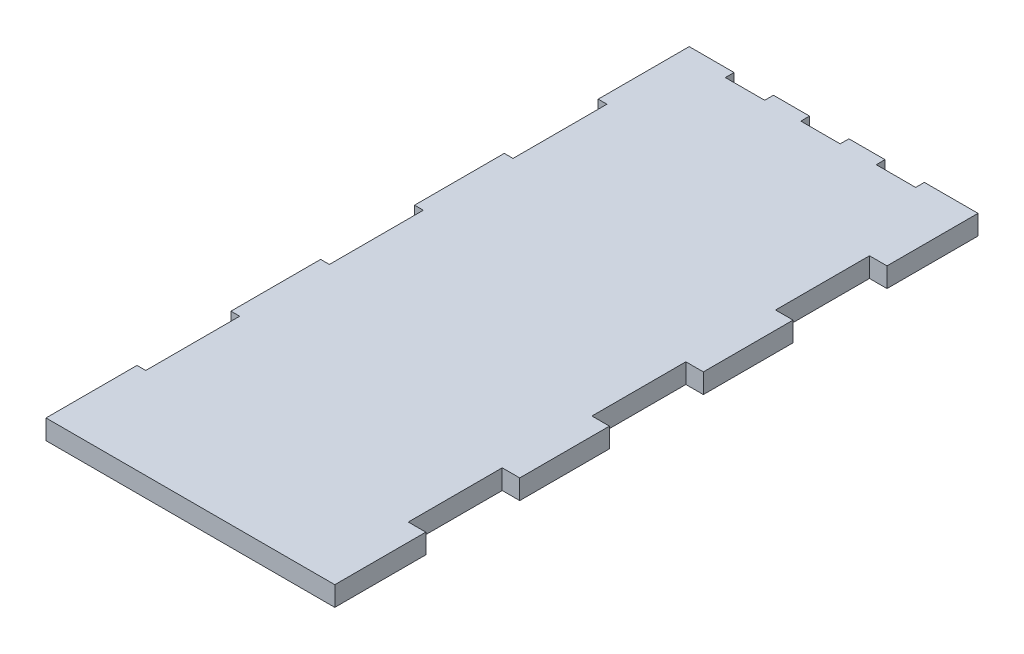
SolidWorks part; units mm, degrees
ref_plane "前视基准面" through (0, 0, 0) normal (0, 0, 1) x (1, 0, 0)
ref_plane "上视基准面" through (0, 0, 0) normal (0, 1, 0) x (1, 0, 0)
ref_plane "右视基准面" through (0, 0, 0) normal (1, 0, 0) x (0, 0, -1)
other "Configuration Table"
sketch "草图4" plane through (0, 0, 0) normal (0, 1, 0) x (1, 0, 0)
  line L6 (-30, -72.5) -> (30, -72.5)
  line L11 (-30, -72.5) -> (-30, 72.5)
  line L12 (-30, 72.5) -> (30, 72.5)
  line L13 (30, -72.5) -> (30, 72.5)
  line L14 (-30, -72.5) -> (30, 72.5) construction
  line L15 (-30, 72.5) -> (30, -72.5) construction
  point P0 (0, 0)
  dimension "D1" = 60
  dimension "D2" = 145
extrude "凸台-拉伸1" add sketch "草图4" along normal blind 4.5
sketch "草图5" plane through (0, 0, -72.5) normal (0, 0, -1) x (-1, 0, 0)
  line L0 (-30, 4.5) -> (30, 4.5) construction
  line L1 (30, 0) -> (21.75, 0)
  line L2 (30, 0) -> (30, 4.5)
  line L3 (30, 4.5) -> (21.75, 4.5)
  line L4 (21.75, 0) -> (21.75, 4.5)
  line L5 (-30, 0) -> (30, 0) construction
  line L6 (12.75, 0) -> (4.5, 0)
  line L7 (12.75, 0) -> (12.75, 4.5)
  line L8 (12.75, 4.5) -> (4.5, 4.5)
  line L9 (4.5, 0) -> (4.5, 4.5)
  line L10 (21.75, 0) -> (12.75, 0)
  line L11 (-4.5, 0) -> (-12.75, 0)
  line L12 (-4.5, 0) -> (-4.5, 4.5)
  line L13 (-4.5, 4.5) -> (-12.75, 4.5)
  line L14 (-12.75, 0) -> (-12.75, 4.5)
  line L15 (-21.75, 0) -> (-30, 0)
  line L16 (-21.75, 0) -> (-21.75, 4.5)
  line L17 (-21.75, 4.5) -> (-30, 4.5)
  line L18 (-30, 0) -> (-30, 4.5)
  line L19 (4.5, 0) -> (-4.5, 0)
  line L20 (-12.75, 0) -> (-21.75, 0)
  line M17 (-30, 0) -> (30, 0)
  line M18 (30, 0) -> (30, 4.5)
  line M19 (30, 4.5) -> (-30, 4.5)
  line M20 (-30, 4.5) -> (-30, 0)
  dimension "D1" = 9
extrude "凸台-拉伸2" add sketch "草图5" along normal blind 2 contours L16 M17 M19 M20 | L14 L12 M17 M19 | L9 L7 M17 M19 | L4 M17 M18 M19 region at (-25.875, 2.25, -72.5) region at (-8.625, 2.25, -72.5) region at (8.625, 2.25, -72.5) region at (25.875, 2.25, -72.5)
sketch "草图7" plane through (30, 0, 0) normal (1, 0, 0) x (0, 0, -1)
  line L0 (-72.5, 4.5) -> (74.5, 4.5) construction
  line L1 (-72.5, 0) -> (-51.7, 0)
  line L2 (-72.5, 0) -> (-72.5, 4.5)
  line L3 (-72.5, 4.5) -> (-51.7, 4.5)
  line L4 (-51.7, 0) -> (-51.7, 4.5)
  line L5 (-72.5, 0) -> (74.5, 0) construction
  line L6 (-30.2333, 0) -> (-9.7333, 0)
  line L7 (-30.2333, 0) -> (-30.2333, 4.5)
  line L8 (-30.2333, 4.5) -> (-9.7333, 4.5)
  line L9 (-9.7333, 0) -> (-9.7333, 4.5)
  line L10 (-51.7, 2.25) -> (-30.2333, 2.25) construction
  line L11 (11.7333, 0) -> (32.2333, 0)
  line L12 (11.7333, 0) -> (11.7333, 4.5)
  line L13 (11.7333, 4.5) -> (32.2333, 4.5)
  line L14 (32.2333, 0) -> (32.2333, 4.5)
  line L15 (53.7, 0) -> (74.5, 0)
  line L16 (53.7, 0) -> (53.7, 4.5)
  line L17 (53.7, 4.5) -> (74.5, 4.5)
  line L18 (74.5, 0) -> (74.5, 4.5)
  line L19 (-9.7333, 2.25) -> (11.7333, 2.25) construction
  line L20 (32.2333, 2.25) -> (53.7, 2.25) construction
  dimension "D1" = 20.8
  dimension "D2" = 20.5
extrude "凸台-拉伸3" add sketch "草图7" along normal blind 4
extrude "凸台-拉伸4" add sketch "草图7<2>" against normal blind 2 from surface starting at face at (-30, 2.25, -1)
sketch "草图7<2>" plane through (30, 0, 0) normal (1, 0, 0) x (0, 0, -1) same geometry as "草图7"
sketch "草图9" plane through (0, 0, 72.5) normal (0, 0, 1) x (1, 0, 0)
  line L0 (-9.8, 0) -> (-11.6, -1.8)
  line L1 (-11.6, -1.8) -> (-9.8, -1.8)
  line L2 (-9.8, -1.8) -> (9.8, -1.8)
  line L3 (9.8, -1.8) -> (11.6, -1.8)
  line L4 (11.6, -1.8) -> (9.8, 0)
  line L5 (-32, 0) -> (34, 0) construction
  line L6 (9.8, 0) -> (9.8, -1.8) construction
  line L7 (-9.8, -1.8) -> (-9.8, 0) construction
  line L8 (-9.8, 0) -> (9.8, 0)
  line L9 (0, 0) -> (0, -1.8) construction
  dimension "D1" = 1.8
  dimension "D2" = 19.6
extrude "凸台-拉伸5" add sketch "草图9" against normal up to surface (145 mm away) from offset 2.2 up to face at (0, 2.25, -72.5) offset against normal yes
